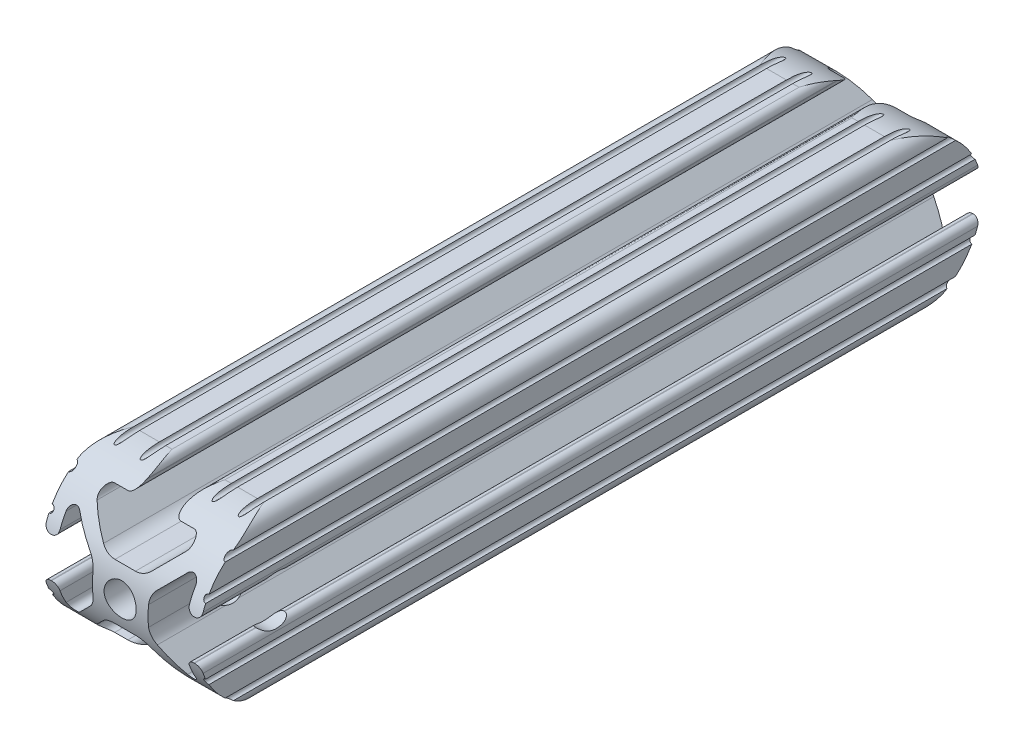
SolidWorks part; units mm, degrees
ref_plane "Front Plane" through (0, 0, 0) normal (0, 0, 1) x (1, 0, 0)
ref_plane "Top Plane" through (0, 0, 0) normal (0, 1, 0) x (1, 0, 0)
ref_plane "Right Plane" through (0, 0, 0) normal (1, 0, 0) x (0, 0, -1)
sketch "Sketch1" plane through (0, 0, 0) normal (0, 0, 1) x (1, 0, 0)
  line L88 (-7.1797, -8.6452) -> (-3.9523, -5.4237)
  line L89 (-1.7093, -4.4958) -> (1.7093, -4.4958)
  line L90 (3.9523, -5.4237) -> (7.1797, -8.6452)
  line L91 (6.4164, -10.4902) -> (4.2875, -10.4902)
  line L92 (3.2385, -11.5392) -> (3.2385, -11.651)
  line L93 (4.2875, -12.7) -> (5.3171, -12.7)
  line L94 (6.3331, -12.7) -> (9.5504, -12.7)
  line L95 (12.7, -9.5504) -> (12.7, -6.3331)
  line L96 (12.7, -5.3171) -> (12.7, -4.2875)
  line L97 (11.651, -3.2385) -> (11.5392, -3.2385)
  line L98 (10.4902, -4.2875) -> (10.4902, -6.4021)
  line L99 (8.7371, -7.1294) -> (5.441, -3.8408)
  line L100 (4.5085, -1.5932) -> (4.5085, 1.5932)
  line L101 (5.441, 3.8408) -> (8.7371, 7.1294)
  line L102 (10.4902, 6.4021) -> (10.4902, 4.2875)
  line L103 (11.5392, 3.2385) -> (11.651, 3.2385)
  line L104 (12.7, 4.2875) -> (12.7, 5.3171)
  line L105 (12.7, 6.3331) -> (12.7, 9.5504)
  line L106 (9.5504, 12.7) -> (6.3331, 12.7)
  line L107 (5.3171, 12.7) -> (4.2875, 12.7)
  line L108 (3.2385, 11.651) -> (3.2385, 11.5392)
  line L109 (4.2875, 10.4902) -> (6.4768, 10.4902)
  line L110 (7.207, 8.7244) -> (3.8983, 5.4232)
  line L111 (1.6558, 4.4958) -> (-1.6558, 4.4958)
  line L112 (-3.8983, 5.4232) -> (-7.207, 8.7244)
  line L113 (-6.4768, 10.4902) -> (-4.2875, 10.4902)
  line L114 (-3.2385, 11.5392) -> (-3.2385, 11.651)
  line L115 (-4.2875, 12.7) -> (-5.3171, 12.7)
  line L116 (-6.3331, 12.7) -> (-9.5504, 12.7)
  line L117 (-12.7, 9.5504) -> (-12.7, 6.3331)
  line L118 (-12.7, 5.3171) -> (-12.7, 4.2875)
  line L119 (-11.651, 3.2385) -> (-11.5392, 3.2385)
  line L120 (-10.4902, 4.2875) -> (-10.4902, 6.4021)
  line L121 (-8.7371, 7.1294) -> (-5.441, 3.8408)
  line L122 (-4.5085, 1.5932) -> (-4.5085, -1.5932)
  line L123 (-5.441, -3.8408) -> (-8.7371, -7.1294)
  line L124 (-10.4902, -6.4021) -> (-10.4902, -4.2875)
  line L125 (-11.5392, -3.2385) -> (-11.651, -3.2385)
  line L126 (-12.7, -4.2875) -> (-12.7, -5.3171)
  line L127 (-12.7, -6.3331) -> (-12.7, -9.5504)
  line L128 (-9.5504, -12.7) -> (-6.3331, -12.7)
  line L129 (-5.3171, -12.7) -> (-4.2875, -12.7)
  line L130 (-3.2385, -11.651) -> (-3.2385, -11.5392)
  line L131 (-4.2875, -10.4902) -> (-6.4164, -10.4902)
  circle A1 centre (0, 0) radius 2.6035
  arc A104 (-7.1797, -8.6452) -> (-6.4164, -10.4902) centre (-6.4164, -9.4098) ccw
  arc A105 (-1.7093, -4.4958) -> (-3.9523, -5.4237) centre (-1.7093, -7.6708) ccw
  arc A106 (3.9523, -5.4237) -> (1.7093, -4.4958) centre (1.7093, -7.6708) ccw
  arc A107 (6.4164, -10.4902) -> (7.1797, -8.6452) centre (6.4164, -9.4098) ccw
  arc A108 (4.2875, -10.4902) -> (3.2385, -11.5392) centre (4.2875, -11.5392) ccw
  arc A109 (3.2385, -11.651) -> (4.2875, -12.7) centre (4.2875, -11.651) ccw
  arc A110 (6.3331, -12.7) -> (5.3171, -12.7) centre (5.8251, -12.7) ccw
  arc A111 (10.5664, -12.6998) -> (9.5504, -12.7) centre (10.0584, -12.7) ccw
  arc A112 (10.5664, -12.6998) -> (12.6998, -10.5664) centre (10.5918, -10.5918) ccw
  arc A113 (12.7, -9.5504) -> (12.6998, -10.5664) centre (12.7, -10.0584) ccw
  arc A114 (12.7, -5.3171) -> (12.7, -6.3331) centre (12.7, -5.8251) ccw
  arc A115 (12.7, -4.2875) -> (11.651, -3.2385) centre (11.651, -4.2875) ccw
  arc A116 (11.5392, -3.2385) -> (10.4902, -4.2875) centre (11.5392, -4.2875) ccw
  arc A117 (8.7371, -7.1294) -> (10.4902, -6.4021) centre (9.4628, -6.4021) ccw
  arc A118 (4.5085, -1.5932) -> (5.441, -3.8408) centre (7.6835, -1.5932) ccw
  arc A119 (5.441, 3.8408) -> (4.5085, 1.5932) centre (7.6835, 1.5932) ccw
  arc A120 (10.4902, 6.4021) -> (8.7371, 7.1294) centre (9.4628, 6.4021) ccw
  arc A121 (10.4902, 4.2875) -> (11.5392, 3.2385) centre (11.5392, 4.2875) ccw
  arc A122 (11.651, 3.2385) -> (12.7, 4.2875) centre (11.651, 4.2875) ccw
  arc A123 (12.7, 6.3331) -> (12.7, 5.3171) centre (12.7, 5.8251) ccw
  arc A124 (12.6998, 10.5664) -> (12.7, 9.5504) centre (12.7, 10.0584) ccw
  arc A125 (12.6998, 10.5664) -> (10.5664, 12.6998) centre (10.5918, 10.5918) ccw
  arc A126 (9.5504, 12.7) -> (10.5664, 12.6998) centre (10.0584, 12.7) ccw
  arc A127 (5.3171, 12.7) -> (6.3331, 12.7) centre (5.8251, 12.7) ccw
  arc A128 (4.2875, 12.7) -> (3.2385, 11.651) centre (4.2875, 11.651) ccw
  arc A129 (3.2385, 11.5392) -> (4.2875, 10.4902) centre (4.2875, 11.5392) ccw
  arc A130 (7.207, 8.7244) -> (6.4768, 10.4902) centre (6.4768, 9.4563) ccw
  arc A131 (1.6558, 4.4958) -> (3.8983, 5.4232) centre (1.6558, 7.6708) ccw
  arc A132 (-3.8983, 5.4232) -> (-1.6558, 4.4958) centre (-1.6558, 7.6708) ccw
  arc A133 (-6.4768, 10.4902) -> (-7.207, 8.7244) centre (-6.4768, 9.4563) ccw
  arc A134 (-4.2875, 10.4902) -> (-3.2385, 11.5392) centre (-4.2875, 11.5392) ccw
  arc A135 (-3.2385, 11.651) -> (-4.2875, 12.7) centre (-4.2875, 11.651) ccw
  arc A136 (-6.3331, 12.7) -> (-5.3171, 12.7) centre (-5.8251, 12.7) ccw
  arc A137 (-10.5664, 12.6998) -> (-9.5504, 12.7) centre (-10.0584, 12.7) ccw
  arc A138 (-10.5664, 12.6998) -> (-12.6998, 10.5664) centre (-10.5918, 10.5918) ccw
  arc A139 (-12.7, 9.5504) -> (-12.6998, 10.5664) centre (-12.7, 10.0584) ccw
  arc A140 (-12.7, 5.3171) -> (-12.7, 6.3331) centre (-12.7, 5.8251) ccw
  arc A141 (-12.7, 4.2875) -> (-11.651, 3.2385) centre (-11.651, 4.2875) ccw
  arc A142 (-11.5392, 3.2385) -> (-10.4902, 4.2875) centre (-11.5392, 4.2875) ccw
  arc A143 (-8.7371, 7.1294) -> (-10.4902, 6.4021) centre (-9.4628, 6.4021) ccw
  arc A144 (-4.5085, 1.5932) -> (-5.441, 3.8408) centre (-7.6835, 1.5932) ccw
  arc A145 (-5.441, -3.8408) -> (-4.5085, -1.5932) centre (-7.6835, -1.5932) ccw
  arc A146 (-10.4902, -6.4021) -> (-8.7371, -7.1294) centre (-9.4628, -6.4021) ccw
  arc A147 (-10.4902, -4.2875) -> (-11.5392, -3.2385) centre (-11.5392, -4.2875) ccw
  arc A148 (-11.651, -3.2385) -> (-12.7, -4.2875) centre (-11.651, -4.2875) ccw
  arc A149 (-12.7, -6.3331) -> (-12.7, -5.3171) centre (-12.7, -5.8251) ccw
  arc A150 (-12.6998, -10.5664) -> (-12.7, -9.5504) centre (-12.7, -10.0584) ccw
  arc A151 (-12.6998, -10.5664) -> (-10.5664, -12.6998) centre (-10.5918, -10.5918) ccw
  arc A152 (-9.5504, -12.7) -> (-10.5664, -12.6998) centre (-10.0584, -12.7) ccw
  arc A153 (-5.3171, -12.7) -> (-6.3331, -12.7) centre (-5.8251, -12.7) ccw
  arc A154 (-4.2875, -12.7) -> (-3.2385, -11.651) centre (-4.2875, -11.651) ccw
  arc A155 (-3.2385, -11.5392) -> (-4.2875, -10.4902) centre (-4.2875, -11.5392) ccw
extrude "Boss-Extrude1" add sketch "Sketch1" along normal mid plane 127
sketch "Sketch2" plane through (12.7, 0, 0) normal (1, 0, 0) x (0, 0, -1)
  line L0 (-63.5, 0) -> (63.5, 0) construction
  line L1 (63.5, -12.7) -> (-63.5, -12.7)
  line L2 (63.5, -12.7) -> (63.5, 12.7)
  line L3 (63.5, 12.7) -> (-63.5, 12.7)
  line L4 (-63.5, -12.7) -> (-63.5, 12.7)
  line L5 (63.5, -12.7) -> (-63.5, 12.7) construction
  line L6 (63.5, 12.7) -> (-63.5, -12.7) construction
  circle A0 centre (-50.8, 0) radius 12.7
  circle A1 centre (50.8, 0) radius 12.7
  circle A2 centre (-50.8, 0) radius 3.9687
  point P0 (0, 0)
  line M7 (63.5, -9.5504) -> (63.5, -6.3331)
  line M8 (63.5, -6.3331) -> (-63.5, -6.3331)
  line M9 (-63.5, -6.3331) -> (-63.5, -9.5504)
  line M10 (-63.5, -9.5504) -> (63.5, -9.5504)
  dimension "D1" = 7.9375
extrude "Cut-Extrude1" cut sketch "Sketch2" against normal through all contours A0 L3 L4 | A0 L4 M8 | A0 M8 M9 M10 | A0 L4 L1 M10 | A1 L1 L2 M10 | A1 M10 M7 M8 | A1 L2 M8 | A1 L2 L3 | A2 region at (12.7, -11.3727, -59.7456) region at (12.7, -8.1865, -61.9688) region at (12.7, -11.3727, 59.7456) region at (12.7, -4.7717, -62.9989) region at (12.7, -8.1865, 61.9688) region at (12.7, 9.8632, -60.6632) region at (12.7, -4.7717, 62.9989) region at (12.7, 9.8632, 60.6632) region at (12.7, 0, 50.8)
